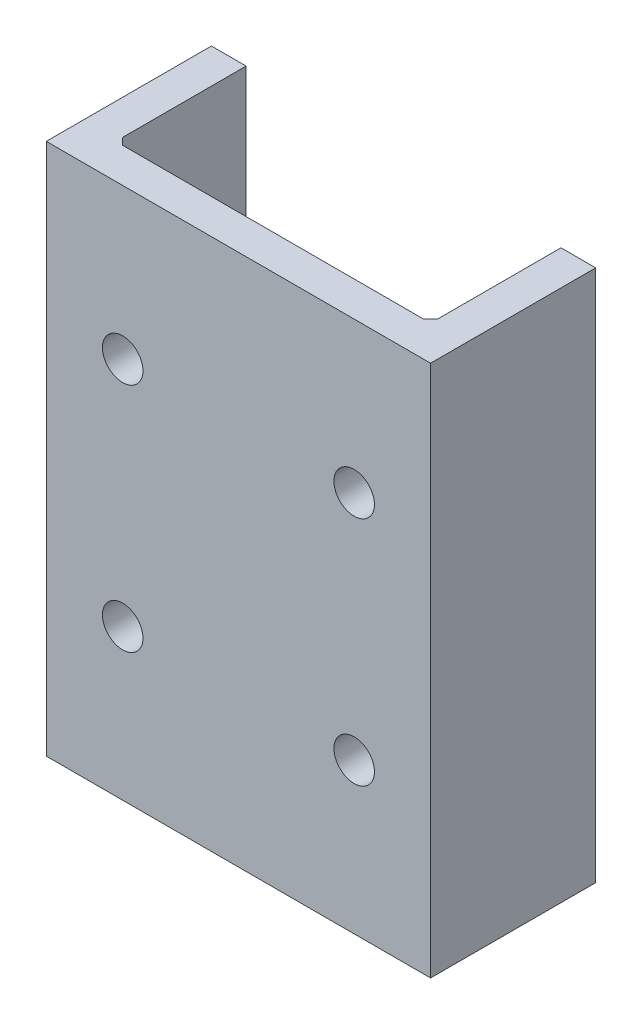
SolidWorks part; units mm, degrees
ref_plane "Plan de face" through (0, 0, 0) normal (0, 0, 1) x (1, 0, 0)
ref_plane "Plan de dessus" through (0, 0, 0) normal (0, 1, 0) x (1, 0, 0)
ref_plane "Plan de droite" through (0, 0, 0) normal (1, 0, 0) x (0, 0, -1)
sketch "Esquisse1" plane through (0, 0, 0) normal (0, 1, 0) x (1, 0, 0)
  line L4 (-13.6, 11.266) -> (-13.6, 0.6)
  line L5 (-13.6, 0.6) -> (-13, 0)
  line L6 (-13, 0) -> (13, 0)
  line L7 (13, 0) -> (13.6, 0.6)
  line L8 (13.6, 0.6) -> (13.6, 11.266)
  line L9 (-13.6, 11.266) -> (-16.6, 11.266)
  line L10 (-16.6, 11.266) -> (-16.6, -3)
  line L11 (-16.6, -3) -> (16.6, -3)
  line L12 (16.6, -3) -> (16.6, 11.266)
  line L13 (16.6, 11.266) -> (13.6, 11.266)
  point P2 (0, 0)
  point P13 (-17.4152, -3.8489)
  dimension "D1" = 27.2
  dimension "D2" = 0.6
  dimension "D3" = 0.6
  dimension "D4" = 3
  dimension "D5" = 3
extrude "Boss.-Extru.1" add sketch "Esquisse1" along normal blind 46
sketch "Esquisse2" plane through (0, 0, 3) normal (0, 0, 1) x (1, 0, 0)
  line L0 (0, 23) -> (0, 0) construction
  line L1 (-10, 13) -> (10, 13) construction
  line L2 (-10, 13) -> (-10, 33) construction
  line L3 (-10, 33) -> (10, 33) construction
  line L4 (10, 13) -> (10, 33) construction
  line L5 (-10, 13) -> (10, 33) construction
  line L6 (-10, 33) -> (10, 13) construction
  line L7 (0, 23) -> (-16.6, 23) construction
  line L8 (-16.6, 46) -> (-16.6, 0) construction
  circle A0 centre (-10, 33) radius 1.75
  circle A1 centre (10, 33) radius 1.75
  circle A2 centre (10, 13) radius 1.75
  circle A3 centre (-10, 13) radius 1.75
  point P0 (0, 23)
  dimension "D1" = 3.5
  dimension "D2" = 20
extrude "Enlèv. mat.-Extru.1" cut sketch "Esquisse2" against normal up to next
